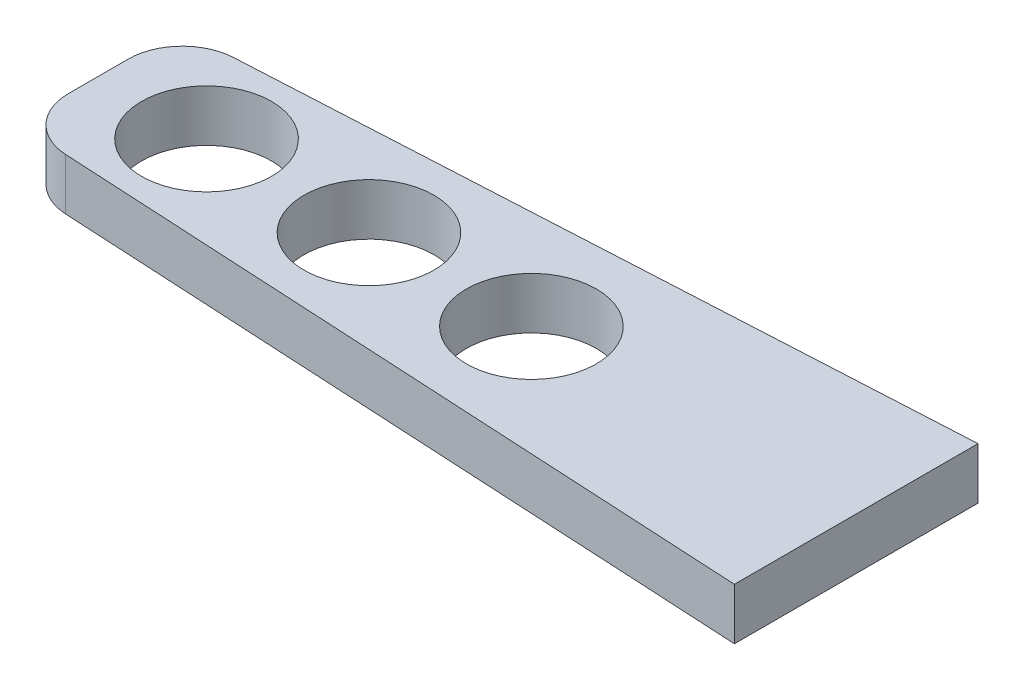
SolidWorks part; units mm, degrees
ref_plane "Front Plane" through (0, 0, 0) normal (0, 0, 1) x (1, 0, 0)
ref_plane "Top Plane" through (0, 0, 0) normal (0, 1, 0) x (1, 0, 0)
ref_plane "Right Plane" through (0, 0, 0) normal (1, 0, 0) x (0, 0, -1)
sketch "Sketch1" plane through (0, 0, 0) normal (0, 1, 0) x (1, 0, 0)
  line L0 (0, -11.25) -> (0, 11.25)
  line L1 (0, 11.25) -> (-70, 7.5)
  line L2 (-70, 7.5) -> (-70, -7.5)
  line L3 (-70, -7.5) -> (0, -11.25)
  line L4 (-70, 0) -> (0, 0) construction
  line L5 (-60, 0) -> (-45, 0) construction
  line L6 (-45, 0) -> (-30, 0) construction
  circle A0 centre (-60, 0) radius 6
  circle A1 centre (-45, 0) radius 6
  circle A2 centre (-30, 0) radius 6
  point P4 (0, 0)
  dimension "D5" = 12
  dimension "D1" = 22.5
  dimension "D2" = 15
  dimension "D3" = 70
  dimension "D4" = 15
  dimension "D6" = 10
extrude "Boss-Extrude1" add sketch "Sketch1" along normal blind 4.7625
fillet "Fillet1" radius 5 2 edges at (-70, 2.3813, 7.5) (-70, 2.3813, -7.5)
equation "\"steeringarmlength\"=70"
equation "\"D3@Sketch1\"=\"steeringarmlength\""
equation "\"mountingholespacing\"=15"
equation "\"D4@Sketch1\"=\"mountingholespacing\""
